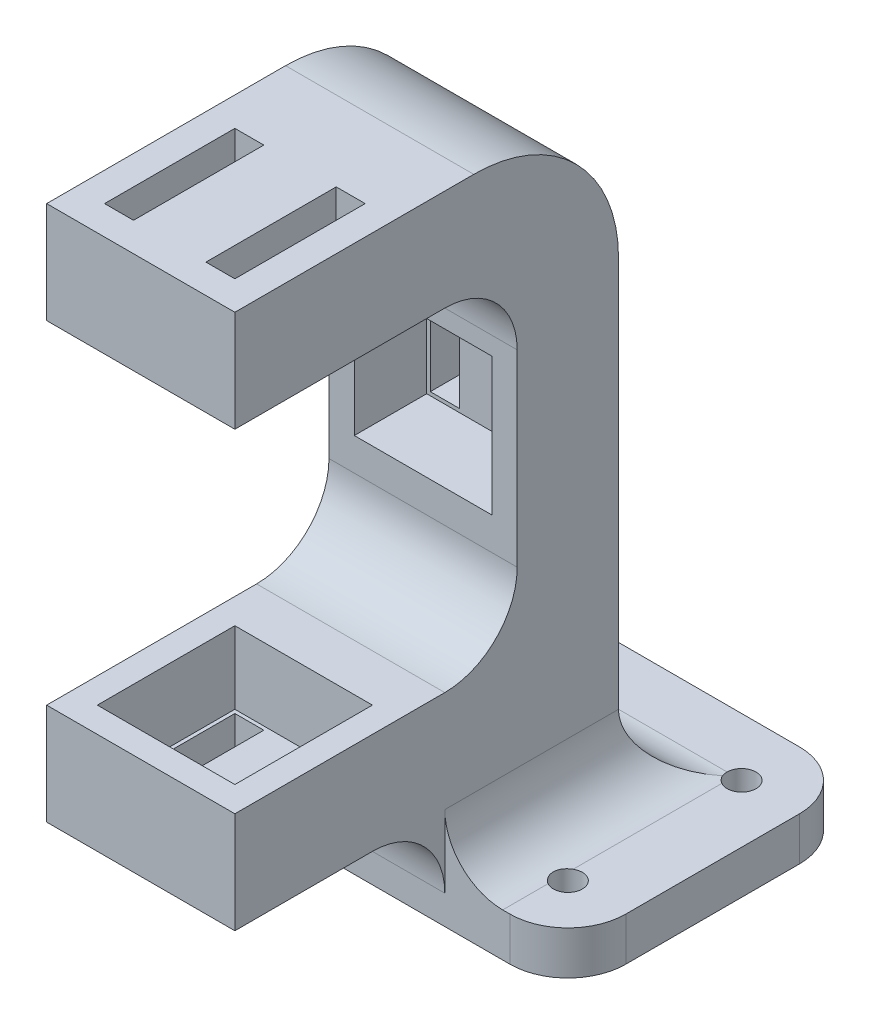
SolidWorks part; units mm, degrees
ref_plane "Front Plane" through (0, 0, 0) normal (0, 0, 1) x (1, 0, 0)
ref_plane "Top Plane" through (0, 0, 0) normal (0, 1, 0) x (1, 0, 0)
ref_plane "Right Plane" through (0, 0, 0) normal (1, 0, 0) x (0, 0, -1)
sketch "Sketch1" plane through (0, -14, 0) normal (0, -1, 0) x (1, 0, 0)
  line L1 (-6.5, -16.5) -> (6.5, -16.5)
  line L2 (6.5, -16.5) -> (6.5, -3.5)
  line L3 (6.5, -3.5) -> (-6.5, -3.5)
  line L4 (-2.5, -5.5) -> (-2.5, -14.5)
  line L5 (-2.5, -14.5) -> (2.5, -14.5)
  line L6 (2.5, -14.5) -> (2.5, -5.5)
  line L7 (2.5, -5.5) -> (-2.5, -5.5)
  line L8 (-2.5, -5.5) -> (-2.5, -14.5)
  line L9 (-2.5, -14.5) -> (2.5, -14.5)
  line L10 (2.5, -14.5) -> (2.5, -5.5)
  line L11 (2.5, -5.5) -> (-2.5, -5.5)
  line L12 (-6.5, -3.5) -> (-6.5, -16.5)
  line L13 (4.5, -14.5) -> (4.5, -5.5)
  line L14 (-4.5, -14.5) -> (4.5, -14.5)
  line L15 (-4.5, -5.5) -> (-4.5, -14.5)
  line L16 (4.5, -5.5) -> (-4.5, -5.5)
  line L17 (4.5, -14.5) -> (4.5, -5.5) construction
  line L18 (-4.5, -14.5) -> (4.5, -14.5) construction
  line L19 (-4.5, -5.5) -> (-4.5, -14.5) construction
  line L20 (4.5, -5.5) -> (-4.5, -5.5) construction
  line L22 (4.5, -5.5) -> (2.5, -5.5)
  line L23 (4.5, -5.5) -> (4.5, -14.5)
  line L24 (4.5, -14.5) -> (2.5, -14.5)
  line L25 (2.5, -5.5) -> (2.5, -14.5)
  line L26 (-4.5, -5.5) -> (-2.5, -5.5)
  line L27 (-4.5, -5.5) -> (-4.5, -14.5)
  line L28 (-4.5, -14.5) -> (-2.5, -14.5)
  line L29 (-2.5, -5.5) -> (-2.5, -14.5)
  line M13 (-2.5, -5.5) -> (-2.5, -14.5)
  line M14 (-2.5, -14.5) -> (2.5, -14.5)
  line M15 (2.5, -14.5) -> (2.5, -5.5)
  line M16 (2.5, -5.5) -> (-2.5, -5.5)
  dimension "D1" = 0
  dimension "D2" = 0
  dimension "D3" = 2
extrude "Boss-Extrude1" add sketch "Sketch1" along normal blind 2 contours L3 L12 L1 L2 L28 L27 L26 L22 L23 L24 M16 M14 | M16 M13 M14 M15 region at (-6.3162, -14, -10) region at (0, -14, -10)
sketch "Sketch2" plane through (0, -14, 0) normal (0, 1, 0) x (1, 0, 0)
  line L0 (-4.75, 5.25) -> (4.75, 5.25)
  line L1 (4.75, 5.25) -> (4.75, 14.75)
  line L2 (4.75, 14.75) -> (-4.75, 14.75)
  line L3 (-4.75, 14.75) -> (-4.75, 5.25)
  line L4 (-6.5, 3.5) -> (6.5, 3.5)
  line L5 (6.5, 3.5) -> (6.5, 16.5)
  line L6 (6.5, 16.5) -> (-6.5, 16.5)
  line L7 (-6.5, 16.5) -> (-6.5, 3.5)
  line L8 (-6.5, 3.5) -> (6.5, 3.5)
  line L9 (6.5, 3.5) -> (6.5, 16.5)
  line L10 (6.5, 16.5) -> (-6.5, 16.5)
  line L11 (-6.5, 16.5) -> (-6.5, 3.5)
  dimension "D1" = 0
  dimension "D2" = 1.75
extrude "Boss-Extrude2" add sketch "Sketch2" along normal blind 5
sketch "Sketch3" plane through (0, 0, -28) normal (0, 0, -1) x (-1, 0, 0)
  line L4 (2.5, -1.5) -> (2.5, 7.5)
  line L5 (2.5, 7.5) -> (-2.5, 7.5)
  line L6 (-2.5, 7.5) -> (-2.5, -1.5)
  line L7 (-2.5, -1.5) -> (2.5, -1.5)
  line L8 (2.5, -1.5) -> (2.5, 7.5)
  line L9 (2.5, 7.5) -> (-2.5, 7.5)
  line L10 (-2.5, 7.5) -> (-2.5, -1.5)
  line L11 (-2.5, -1.5) -> (2.5, -1.5)
  line L12 (-4.5, 7.5) -> (-4.5, -1.5)
  line L13 (4.5, 7.5) -> (-4.5, 7.5)
  line L14 (4.5, -1.5) -> (4.5, 7.5)
  line L15 (-4.5, -1.5) -> (4.5, -1.5)
  line L16 (-4.5, 7.5) -> (-4.5, -1.5)
  line L17 (4.5, 7.5) -> (-4.5, 7.5)
  line L18 (4.5, -1.5) -> (4.5, 7.5)
  line L19 (-4.5, -1.5) -> (4.5, -1.5)
  line L24 (-6.5, 9.5) -> (-6.5, -3.5)
  line L25 (6.5, 9.5) -> (-6.5, 9.5)
  line L26 (6.5, -3.5) -> (6.5, 9.5)
  line L27 (-6.5, -3.5) -> (6.5, -3.5)
  line L28 (-6.5, 9.5) -> (-6.5, -3.5)
  line L29 (6.5, 9.5) -> (-6.5, 9.5)
  line L30 (6.5, -3.5) -> (6.5, 9.5)
  line L31 (-6.5, -3.5) -> (6.5, -3.5)
  line M13 (2.5, -1.5) -> (2.5, 7.5)
  line M14 (2.5, 7.5) -> (-2.5, 7.5)
  line M15 (-2.5, 7.5) -> (-2.5, -1.5)
  line M16 (-2.5, -1.5) -> (2.5, -1.5)
  dimension "D1" = 0
  dimension "D2" = 0
  dimension "D3" = 2
extrude "Boss-Extrude3" add sketch "Sketch3" along normal blind 2 separate body contours M16 M13 M14 M15 | L28 L31 L30 L29 L19 L16 L17 L18 M14 M16 region at (0, 3, -28) region at (0, 9.3162, -28)
sketch "Sketch4" plane through (0, 0, -28) normal (0, 0, 1) x (1, 0, 0)
  line L4 (6.5, -3.5) -> (6.5, 9.5)
  line L5 (6.5, 9.5) -> (-6.5, 9.5)
  line L6 (-6.5, 9.5) -> (-6.5, -3.5)
  line L7 (-6.5, -3.5) -> (6.5, -3.5)
  line L8 (6.5, -3.5) -> (6.5, 9.5)
  line L9 (6.5, 9.5) -> (-6.5, 9.5)
  line L10 (-6.5, 9.5) -> (-6.5, -3.5)
  line L11 (-6.5, -3.5) -> (6.5, -3.5)
  line L20 (4.75, -1.75) -> (4.75, 7.75)
  line L21 (4.75, 7.75) -> (-4.75, 7.75)
  line L22 (-4.75, 7.75) -> (-4.75, -1.75)
  line L23 (-4.75, -1.75) -> (4.75, -1.75)
  line L24 (4.75, -1.75) -> (4.75, 7.75)
  line L25 (4.75, 7.75) -> (-4.75, 7.75)
  line L26 (-4.75, 7.75) -> (-4.75, -1.75)
  line L27 (-4.75, -1.75) -> (4.75, -1.75)
  dimension "D1" = 0
  dimension "D2" = 1.75
extrude "Boss-Extrude4" add sketch "Sketch4" along normal blind 5
sketch "Sketch5" plane through (0, 19, 0) normal (0, 1, 0) x (1, 0, 0)
  line L4 (-2.5, 14.5) -> (-2.5, 5.5)
  line L5 (-2.5, 5.5) -> (2.5, 5.5)
  line L6 (2.5, 5.5) -> (2.5, 14.5)
  line L7 (2.5, 14.5) -> (-2.5, 14.5)
  line L8 (-2.5, 14.5) -> (-2.5, 5.5)
  line L9 (-2.5, 5.5) -> (2.5, 5.5)
  line L10 (2.5, 5.5) -> (2.5, 14.5)
  line L11 (2.5, 14.5) -> (-2.5, 14.5)
  line L12 (4.5, 5.5) -> (4.5, 14.5)
  line L13 (-4.5, 5.5) -> (4.5, 5.5)
  line L14 (-4.5, 14.5) -> (-4.5, 5.5)
  line L15 (4.5, 14.5) -> (-4.5, 14.5)
  line L16 (4.5, 5.5) -> (4.5, 14.5)
  line L17 (-4.5, 5.5) -> (4.5, 5.5)
  line L18 (-4.5, 14.5) -> (-4.5, 5.5)
  line L19 (4.5, 14.5) -> (-4.5, 14.5)
  line L24 (6.5, 3.5) -> (6.5, 16.5)
  line L25 (-6.5, 3.5) -> (6.5, 3.5)
  line L26 (-6.5, 16.5) -> (-6.5, 3.5)
  line L27 (6.5, 16.5) -> (-6.5, 16.5)
  line L28 (6.5, 3.5) -> (6.5, 16.5)
  line L29 (-6.5, 3.5) -> (6.5, 3.5)
  line L30 (-6.5, 16.5) -> (-6.5, 3.5)
  line L31 (6.5, 16.5) -> (-6.5, 16.5)
  line M13 (-2.5, 14.5) -> (-2.5, 5.5)
  line M14 (-2.5, 5.5) -> (2.5, 5.5)
  line M15 (2.5, 5.5) -> (2.5, 14.5)
  line M16 (2.5, 14.5) -> (-2.5, 14.5)
  dimension "D1" = 0
  dimension "D2" = 0
  dimension "D3" = 2
extrude "Boss-Extrude5" add sketch "Sketch5" along normal blind 2 separate body contours L28 L31 L30 L29 L19 L16 L17 L18 M14 M16 | M16 M13 M14 M15 region at (0, 19, -10) region at (0, 19, -3.6838)
sketch "Sketch6" plane through (0, 19, 0) normal (0, -1, 0) x (1, 0, 0)
  line L0 (4.75, -14.75) -> (4.75, -5.25)
  line L1 (4.75, -5.25) -> (-4.75, -5.25)
  line L2 (-4.75, -5.25) -> (-4.75, -14.75)
  line L3 (-4.75, -14.75) -> (4.75, -14.75)
  line L4 (6.5, -16.5) -> (6.5, -3.5)
  line L5 (6.5, -3.5) -> (-6.5, -3.5)
  line L6 (-6.5, -3.5) -> (-6.5, -16.5)
  line L7 (-6.5, -16.5) -> (6.5, -16.5)
  line L16 (6.5, -16.5) -> (6.5, -3.5)
  line L17 (6.5, -3.5) -> (-6.5, -3.5)
  line L18 (-6.5, -3.5) -> (-6.5, -16.5)
  line L19 (-6.5, -16.5) -> (6.5, -16.5)
  dimension "D1" = 0
  dimension "D2" = 1.75
extrude "Boss-Extrude6" add sketch "Sketch6" along normal blind 5
sketch "Sketch7" plane through (0, -3.5, 0) normal (0, -1, 0) x (1, 0, 0)
  line L4 (6.5, -30) -> (6.5, -23)
  line L5 (6.5, -23) -> (-6.5, -23)
  line L6 (-6.5, -23) -> (-6.5, -30)
  line L7 (-6.5, -30) -> (6.5, -30)
  line L8 (6.5, -30) -> (6.5, -23)
  line L9 (6.5, -23) -> (-6.5, -23)
  line L10 (-6.5, -23) -> (-6.5, -30)
  line L11 (-6.5, -30) -> (6.5, -30)
  dimension "D1" = 0
extrude "Boss-Extrude7" add sketch "Sketch7" along normal up to surface (12.5 mm away) up to face at (3.5, -16, -10)
sketch "Sketch8" plane through (0, 9.5, 0) normal (0, 1, 0) x (1, 0, 0)
  line L4 (-6.5, 30) -> (-6.5, 23)
  line L5 (-6.5, 23) -> (6.5, 23)
  line L6 (6.5, 23) -> (6.5, 30)
  line L7 (6.5, 30) -> (-6.5, 30)
  line L8 (-6.5, 30) -> (-6.5, 23)
  line L9 (-6.5, 23) -> (6.5, 23)
  line L10 (6.5, 23) -> (6.5, 30)
  line L11 (6.5, 30) -> (-6.5, 30)
  dimension "D1" = 0
extrude "Boss-Extrude8" add sketch "Sketch8" along normal up to surface (11.5 mm away) up to face at (-3.5, 21, -10)
sketch "Sketch9" plane through (0, 0, -16.5) normal (0, 0, -1) x (-1, 0, 0)
  line L4 (6.5, -16) -> (6.5, -9)
  line L5 (6.5, -9) -> (-6.5, -9)
  line L6 (-6.5, -9) -> (-6.5, -16)
  line L7 (-6.5, -16) -> (6.5, -16)
  line L8 (6.5, -16) -> (6.5, -9)
  line L9 (6.5, -9) -> (-6.5, -9)
  line L10 (-6.5, -9) -> (-6.5, -16)
  line L11 (-6.5, -16) -> (6.5, -16)
  line L12 (-6.5, 21) -> (-6.5, 14)
  line L13 (-6.5, 14) -> (6.5, 14)
  line L14 (6.5, 14) -> (6.5, 21)
  line L15 (6.5, 21) -> (-6.5, 21)
  line L16 (-6.5, 21) -> (-6.5, 14)
  line L17 (-6.5, 14) -> (6.5, 14)
  line L18 (6.5, 14) -> (6.5, 21)
  line L19 (6.5, 21) -> (-6.5, 21)
  dimension "D1" = 0
  dimension "D2" = 0
extrude "Boss-Extrude9" add sketch "Sketch9" along normal up to next
sketch "Sketch10" plane through (0, -16, 0) normal (0, -1, 0) x (1, 0, 0)
  line L0 (-6.5, -3.5) -> (-6.5, -30) construction
  line L1 (6.5, -30) -> (-6.5, -30)
  line L2 (6.5, -30) -> (6.5, -18)
  line L3 (6.5, -18) -> (-6.5, -18)
  line L4 (-6.5, -30) -> (-6.5, -18)
  dimension "D1" = 12
extrude "Boss-Extrude10" add sketch "Sketch10" along normal blind 7
sketch "Sketch11" plane through (0, -23, 0) normal (0, -1, 0) x (1, 0, 0)
  line L0 (6.5, -18) -> (-6.5, -18) construction
  line L1 (-15, -38) -> (15, -38)
  line L2 (-15, -38) -> (-15, -18)
  line L3 (-15, -18) -> (15, -18)
  line L4 (15, -38) -> (15, -18)
  point P4 (19.6134, -22.0883)
  point P7 (0, -38)
  dimension "D1" = 30
  dimension "D2" = 20
extrude "Boss-Extrude11" add sketch "Sketch11" against normal blind 3
fillet "Fillet1" radius 4 7 edges at (6.5, -20, -24) (-6.5, -20, -24) (0, -20, -30) (-15, -21.5, -18) (-15, -21.5, -38) (15, -21.5, -18) (15, -21.5, -38)
sketch "Sketch12" plane through (0, -23, 0) normal (0, -1, 0) x (1, 0, 0)
  circle A0 centre (-11, -22) radius 1
  circle A1 centre (11, -22) radius 1
  circle A2 centre (11, -34) radius 1
  circle A3 centre (-11, -34) radius 1
  arc A4 (-11, -18) -> (-15, -22) centre (-11, -22) ccw construction
  arc A5 (-15, -34) -> (-11, -38) centre (-11, -34) ccw construction
  arc A6 (15, -22) -> (11, -18) centre (11, -22) ccw construction
  arc A7 (11, -38) -> (15, -34) centre (11, -34) ccw construction
  point P8 (0, 0)
  dimension "D1" = 2
extrude "Cut-Extrude1" cut sketch "Sketch12" against normal up to next
fillet "Fillet2" radius 10 1 edges at (0, 21, -30)
fillet "Fillet3" radius 5 3 edges at (0, 14, -23) (0, -16, -18) (0, -9, -23)
